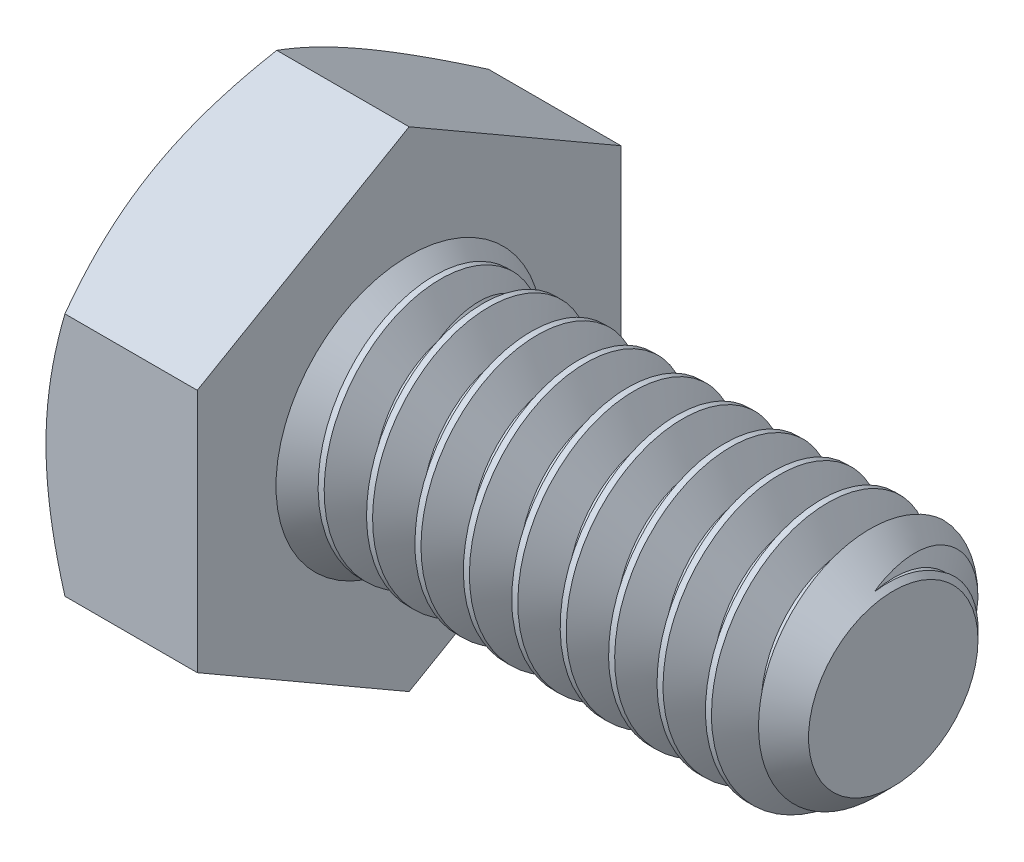
SolidWorks part; units mm, degrees
ref_plane "Front Plane" through (0, 0, 0) normal (0, 0, 1) x (1, 0, 0)
ref_plane "Top Plane" through (0, 0, 0) normal (0, 1, 0) x (1, 0, 0)
ref_plane "Right Plane" through (0, 0, 0) normal (1, 0, 0) x (0, 0, -1)
sketch "Sketch1" plane through (0, 0, 0) normal (0, 0, 1) x (1, 0, 0)
  line L0 (-8.3344, 0) -> (8.3344, 0) construction
  line L1 (8.3344, 3.175) -> (8.3344, -3.175) construction
  line L2 (-4.3656, 5.5562) -> (-4.3656, -5.5562) construction
  line L3 (-8.3344, 5.5562) -> (-8.3344, -5.5562) construction
  line L4 (9.525, -3.3125) -> (8.89, -2.2126) construction
  line L5 (8.89, -2.2126) -> (8.255, -3.3125) construction
  line L6 (8.255, -3.3125) -> (9.525, -3.3125) construction
  line L7 (9.4456, -3.175) -> (8.3344, -3.175) construction
  line L8 (8.89, -3.3125) -> (8.89, -3.175) construction
  line L9 (8.89, -3.175) -> (8.89, -2.3501) construction
  line L10 (8.89, -2.3501) -> (8.89, -2.2126) construction
  line L15 (8.9694, -2.3501) -> (8.8106, -2.3501)
  line L16 (9.4853, -3.2437) -> (8.2947, -3.2437)
  line L17 (8.8106, -2.3501) -> (8.2947, -3.2437)
  line L18 (8.9694, -2.3501) -> (9.4853, -3.2437)
  point P9 (-4.3656, 0)
  point P10 (3.3955, -3.175)
  point P24 (8.89, -3.2437)
  dimension "Head Ht" = 3.9688
  dimension "D1" = 4.9389
  dimension "Pitch" = 1.27
  dimension "D3" = 0.1588
  dimension "Head Width" = 11.1125
  dimension "Length" = 12.7
  dimension "Screw Size" = 6.35
ref_plane "Plane2" through (8.3344, 0, 0) normal (1, 0, 0) x (0, 0, -1)
sketch "Sketch5" plane through (8.3344, 0, 0) normal (1, 0, 0) x (0, 0, -1)
  circle A0 centre (0, 0) radius 3.175
extrude "Boss-Extrude3" add sketch "Sketch5" against normal up to vertex (12.7 mm away) up to point (-4.3656, 0, 0)
chamfer "Chamfer1" distance 0.9525 angle 45 1 edges at (8.3344, 0, -3.175)
sketch "Sketch6" plane through (-4.3656, 0, 0) normal (-1, 0, 0) x (0, 0, 1)
  line L0 (0, 5.5562) -> (0, -5.5562) construction
  line L1 (5.5562, 3.2079) -> (0, 6.4158)
  line L2 (0, 6.4158) -> (-5.5563, 3.2079)
  line L3 (-5.5563, 3.2079) -> (-5.5562, -3.2079)
  line L4 (-5.5562, -3.2079) -> (0, -6.4158)
  line L5 (0, -6.4158) -> (5.5563, -3.2079)
  line L6 (5.5563, -3.2079) -> (5.5562, 3.2079)
  circle A0 centre (0, 0) radius 5.5562 construction
extrude "Boss-Extrude4" add sketch "Sketch6" along normal up to vertex (3.9688 mm away) up to point (-8.3344, -5.5562, 0)
sketch "Sketch7" plane through (-8.3344, 0, 0) normal (-1, 0, 0) x (0, 0, 1)
  circle A0 centre (0, 0) radius 5.5562 construction
  circle A1 centre (0, 0) radius 5.5562
sketch "Sketch8" plane through (-8.3344, 0, 0) normal (-1, 0, 0) x (0, 0, 1)
  circle A0 centre (0, 0) radius 5.5562 construction
  circle A1 centre (0, 0) radius 5.5562
extrude "Cut-Extrude3" cut sketch "Sketch8" against normal through all draft 60 flip side to cut
split "Split1" bodies to split 113 resulting bodies 118 119 split by face at (-4.3656, 0, 3.175)
sketch "Sketch9" plane through (8.3344, 0, 0) normal (1, 0, 0) x (0, 0, -1)
  circle A0 centre (0, 0) radius 3.175 construction
  circle A1 centre (0, 0) radius 3.175
curve "Helix/Spiral1" pitch 1.27 height 13.97 radius 3.175 centre (8.3344, 0, 0) axis (-1, 0, 0) start towards (0, 0, -1)
sketch "Sketch10" plane through (0, 0, 0) normal (0, 0, 1) x (1, 0, 0)
  line L8 (8.9694, -2.3501) -> (8.8106, -2.3501) construction
  line L9 (8.8106, -2.3501) -> (8.2947, -3.2437) construction
  line L10 (9.4853, -3.2437) -> (8.2947, -3.2437) construction
  line L11 (8.9694, -2.3501) -> (9.4853, -3.2437) construction
  line L12 (8.9694, -2.3501) -> (8.8106, -2.3501)
  line L13 (8.8106, -2.3501) -> (8.2947, -3.2437)
  line L14 (9.4853, -3.2437) -> (8.2947, -3.2437)
  line L15 (8.9694, -2.3501) -> (9.4853, -3.2437)
sweep "Cut-Sweep1" cut profiles "Sketch10" path "Helix/Spiral1" align with end faces yes
combine bodies "Combine1" operation type add bodies to combine 119 120
sketch "Sketch11" plane through (-4.3656, 0, 0) normal (1, 0, 0) x (0, 0, -1)
  line L0 (0, 5.5562) -> (0, -5.5562) construction
  circle A0 centre (0, 0) radius 3.4925
  point P3 (0, -3.4925)
  dimension "D1" = 0.3175
extrude "Boss-Extrude5" add sketch "Sketch11" along normal through all draft 45
equation "\"D3@Helix/Spiral1\"= \"Length@Sketch1\" + \"Pitch@Sketch1\""
equation "\"D1@Chamfer1\" = \"Pitch@Sketch1\" * .75"
equation "\"D4@Helix/Spiral1\"=\"Pitch@Sketch1\""
equation "\"D3@Sketch1\" = \"Pitch@Sketch1\" / 8"
equation "\"D1@Sketch11\"=\"Pitch@Sketch1\"/4"
